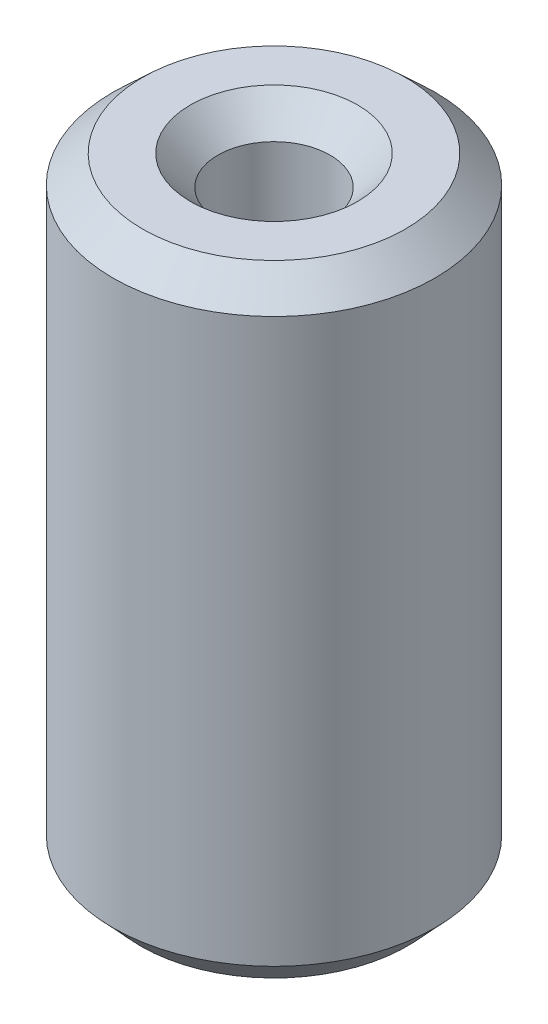
SolidWorks part; units mm, degrees
ref_plane "Front Plane" through (0, 0, 0) normal (0, 0, 1) x (1, 0, 0)
ref_plane "Top Plane" through (0, 0, 0) normal (0, 1, 0) x (1, 0, 0)
ref_plane "Right Plane" through (0, 0, 0) normal (1, 0, 0) x (0, 0, -1)
sketch "Sketch1" plane through (0, 0, 0) normal (0, 1, 0) x (1, 0, 0)
  circle A0 centre (0, 0) radius 12.5
  dimension "SLEEVE_OD" = 25
extrude "Boss-Extrude1" add sketch "Sketch1" along normal blind 48.1297
sketch "Sketch2" plane through (0, 0, 0) normal (0, 1, 0) x (1, 0, 0)
  circle A0 centre (0, 0) radius 4.3514
  dimension "BORE_D" = 8.7029
extrude "Cut-Extrude1" cut sketch "Sketch2" along normal through all
chamfer "Chamfer1" distance 2.1428 angle 47.004 4 edges at (0, 48.1297, 4.3514) (0, 0, 4.3514) (0, 0, 12.5) (0, 48.1297, 12.5) first distance on face at (0, 48.1297, 4.3514) first distance on face at (0, 0, 4.3514) first distance on face at (0, 48.1297, 12.5)
